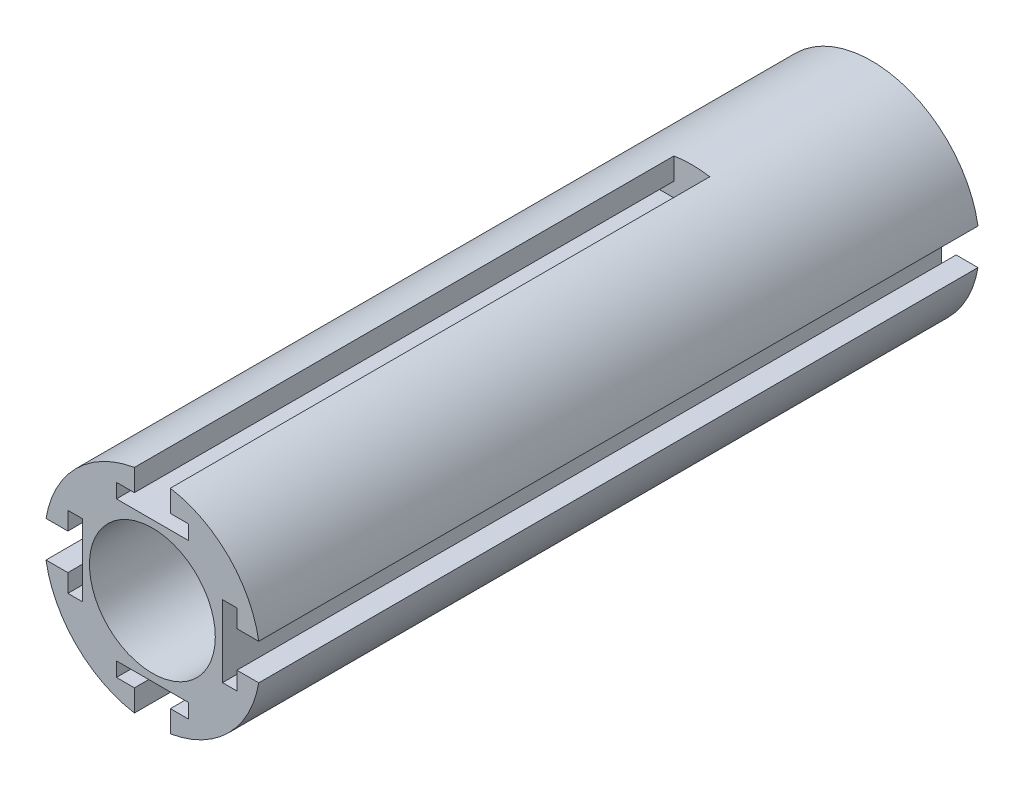
SolidWorks part; units mm, degrees
ref_plane "Front Plane" through (0, 0, 0) normal (0, 0, 1) x (1, 0, 0)
ref_plane "Top Plane" through (0, 0, 0) normal (0, 1, 0) x (1, 0, 0)
ref_plane "Right Plane" through (0, 0, 0) normal (1, 0, 0) x (0, 0, -1)
sketch "Sketch1" plane through (0, 0, 0) normal (0, 0, 1) x (1, 0, 0)
  circle A0 centre (0, 0) radius 30
  circle A1 centre (0, 0) radius 17.5
  dimension "D1" = 60
  dimension "D2" = 35
extrude "Boss-Extrude1" add sketch "Sketch1" along normal blind 200
sketch "Sketch2" plane through (0, 0, 200) normal (0, 0, 1) x (1, 0, 0)
  line L0 (0, 47.4895) -> (0, -45.7743) construction
  line L1 (-53.6709, 0) -> (54.47, 0) construction
  line L2 (-10, 19.5) -> (10, 19.5)
  line L3 (-10, 19.5) -> (-10, 23.5)
  line L4 (10, 19.5) -> (10, 23.5)
  line L5 (-10, 23.5) -> (-5, 23.5)
  line L6 (10, 23.5) -> (5, 23.5)
  line L7 (-5, 23.5) -> (-5, 29.5804)
  line L8 (10, 40) -> (-10, 40)
  line L9 (5, 23.5) -> (5, 29.5804)
  line L24 (5, -39.5034) -> (5.4359, -39.5034)
  line L25 (10, -23.5) -> (5, -23.5)
  line L26 (10, -19.5) -> (10, -23.5)
  line L27 (-10, -19.5) -> (10, -19.5)
  line L28 (-10, -19.5) -> (-10, -23.5)
  line L29 (-10, -23.5) -> (-5, -23.5)
  line L30 (-5, -23.5) -> (-5, -29.5804)
  line L31 (10, -40) -> (-10, -40)
  line L32 (5, -23.5) -> (5, -29.5804)
  line L33 (23.5, -5) -> (29.5804, -5)
  line L34 (40, -10) -> (40, 10)
  line L35 (23.5, 5) -> (29.5804, 5)
  line L36 (23.5, 10) -> (23.5, 5)
  line L37 (19.5, 10) -> (23.5, 10)
  line L38 (19.5, 10) -> (19.5, -10)
  line L39 (19.5, -10) -> (23.5, -10)
  line L40 (23.5, -10) -> (23.5, -5)
  line L41 (-5, -23.5) -> (-5, -29.5804)
  line L42 (-10, -40) -> (10, -40)
  line L43 (5, -23.5) -> (5, -29.5804)
  line L44 (10, -23.5) -> (5, -23.5)
  line L45 (10, -19.5) -> (10, -23.5)
  line L46 (10, -19.5) -> (-10, -19.5)
  line L47 (-10, -19.5) -> (-10, -23.5)
  line L48 (-10, -23.5) -> (-5, -23.5)
  line L49 (-23.5, 5) -> (-29.5804, 5)
  line L50 (-40, 10) -> (-40, -10)
  line L51 (-23.5, -5) -> (-29.5804, -5)
  line L52 (-23.5, -10) -> (-23.5, -5)
  line L53 (-19.5, -10) -> (-23.5, -10)
  line L54 (-19.5, -10) -> (-19.5, 10)
  line L55 (-19.5, 10) -> (-23.5, 10)
  line L56 (-23.5, 10) -> (-23.5, 5)
  circle A0 centre (0, 0) radius 30 construction
  arc A1 (-5, 29.5804) -> (-14.9967, 25.9827) centre (0, 0) ccw
  arc A2 (-10, 40) -> (-14.9967, 25.9827) centre (-32.1599, 40) cw
  arc A3 (5, 29.5804) -> (14.9967, 25.9827) centre (0, 0) cw
  arc A4 (10, 40) -> (14.9967, 25.9827) centre (32.1599, 40) ccw
  arc A10 (-5, 29.5804) -> (5, 29.5804) centre (0, 0) cw
  arc A11 (-5, -29.5804) -> (-14.9967, -25.9827) centre (0, 0) cw
  arc A12 (-10, -40) -> (-14.9967, -25.9827) centre (-32.1599, -40) ccw
  arc A13 (10, -40) -> (14.9967, -25.9827) centre (32.1599, -40) cw
  arc A14 (5, -29.5804) -> (14.9967, -25.9827) centre (0, 0) ccw
  arc A15 (29.5804, -5) -> (25.9827, -14.9967) centre (0, 0) cw
  arc A16 (40, -10) -> (25.9827, -14.9967) centre (40, -32.1599) ccw
  arc A17 (40, 10) -> (25.9827, 14.9967) centre (40, 32.1599) cw
  arc A18 (29.5804, 5) -> (25.9827, 14.9967) centre (0, 0) ccw
  arc A19 (-5, -29.5804) -> (-14.9967, -25.9827) centre (0, 0) cw
  arc A20 (-10, -40) -> (-14.9967, -25.9827) centre (-32.1599, -40) ccw
  arc A21 (10, -40) -> (14.9967, -25.9827) centre (32.1599, -40) cw
  arc A22 (5, -29.5804) -> (14.9967, -25.9827) centre (0, 0) ccw
  arc A23 (-29.5804, 5) -> (-25.9827, 14.9967) centre (0, 0) cw
  arc A24 (-40, 10) -> (-25.9827, 14.9967) centre (-40, 32.1599) ccw
  arc A25 (-40, -10) -> (-25.9827, -14.9967) centre (-40, -32.1599) cw
  arc A26 (-29.5804, -5) -> (-25.9827, -14.9967) centre (0, 0) ccw
  circle A27 centre (0, 0) radius 17.5 construction
  point P5 (0, 30)
  point P6 (0, 17.5)
  point P9 (0, 22)
  point P13 (0, 19.5)
  point P17 (-14.8156, 26.0864)
  point P19 (-14.8156, 26.0864)
  point P22 (0, 40)
  point P23 (0, 30)
  point P29 (0, 40)
  point P47 (-10, 14.3614)
  point P93 (0, 0)
  circle M33 centre (0, 0) radius 30
  dimension "D9" = 4
  dimension "D7" = 20
  dimension "D1" = 2
  dimension "D3" = 20
  dimension "D4" = 4
  dimension "D5" = 10
  dimension "D6" = 10
  dimension "D8" = 5
extrude "Cut-Extrude1" cut sketch "Sketch2" against normal blind 150 contours L6 L9 L7 L5 L3 L2 L4 M33 region at (0, 23.795, 200)
extrude "Cut-Extrude2" cut sketch "Sketch2<3>" against normal blind 50 contours L32 L25 L26 L27 L28 L29 L30 M33 region at (0, -23.795, 200)
sketch "Sketch2<3>" plane through (0, 0, 200) normal (0, 0, 1) x (1, 0, 0) same geometry as "Sketch2"
ref_plane "Plane1" through (0, 0, 100) normal (0, 0, 1) x (1, 0, 0)
mirror "Mirror1" about plane through (0, 0, 100) normal (0, 0, 1) of "Cut-Extrude2"
extrude "Cut-Extrude3" cut sketch "Sketch2<5>" against normal through all contours L55 L56 L49 L51 L52 L53 L54 M33 | L39 L40 L33 L35 L36 L37 L38 M33 region at (-23.795, 0, 200) region at (23.795, 0, 200)
sketch "Sketch2<5>" plane through (0, 0, 200) normal (0, 0, 1) x (1, 0, 0) same geometry as "Sketch2"
